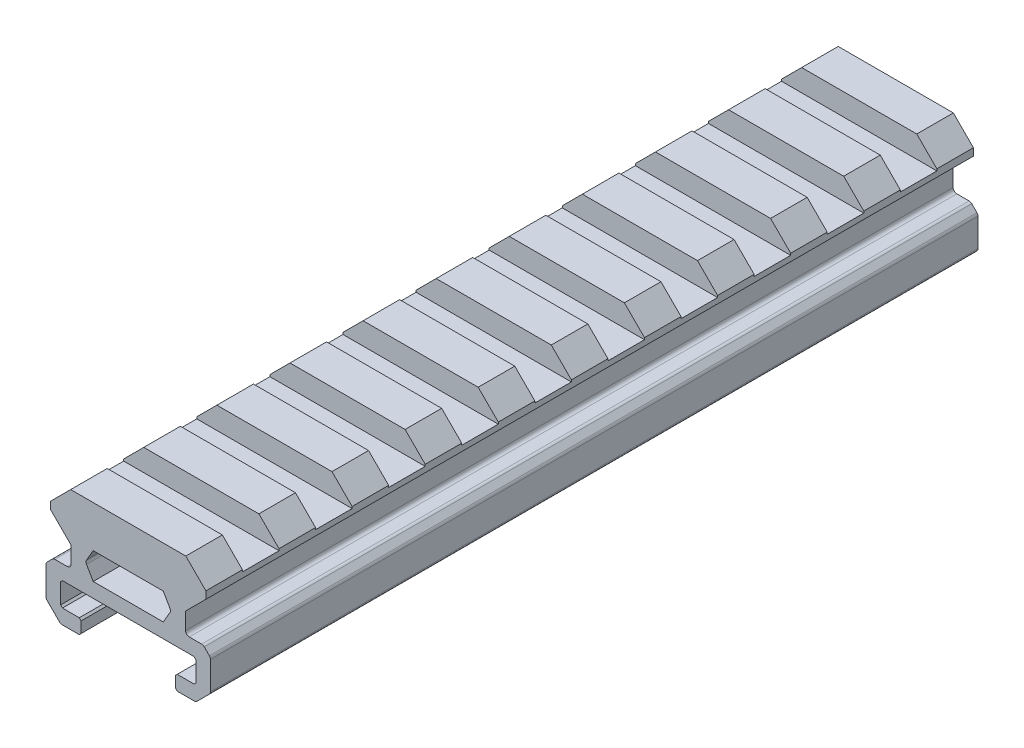
SolidWorks part; units mm, degrees
ref_plane "Front Plane" through (0, 0, 0) normal (0, 0, 1) x (1, 0, 0)
ref_plane "Bottom Plane" through (0, 0, 0) normal (0, 1, 0) x (1, 0, 0)
ref_plane "Right Plane" through (0, 0, 0) normal (1, 0, 0) x (0, 0, -1)
sketch "Sketch1" plane through (0, 0, 0) normal (0, 0, 1) x (1, 0, 0)
  line L0 (7.875, 11.35) -> (10.625, 8.6)
  line L1 (10.625, 7.6) -> (10.625, 8.6)
  line L2 (10.625, 7.6) -> (7.875, 4.85)
  line L3 (7.875, 4.85) -> (7.85, 4.85)
  line L4 (7.85, 4.85) -> (7.85, 2)
  line L5 (7.85, 2) -> (10.25, 2)
  line L6 (11.25, 1) -> (10.25, 2)
  line L7 (11.25, -3.25) -> (11.25, 1)
  line L8 (11.25, -3.25) -> (9.25, -5.25)
  line L9 (9.25, -5.25) -> (6.45, -5.25)
  line L10 (6.45, -5.25) -> (6.45, -3.25)
  line L11 (9.25, -3.25) -> (6.45, -3.25)
  line L14 (9.25, -3.25) -> (9.25, 0)
  line L18 (9.25, 0) -> (-9.25, 0)
  line L19 (-9.25, -3.25) -> (-9.25, 0)
  line L20 (-9.25, -3.25) -> (-6.45, -3.25)
  line L21 (-6.45, -5.25) -> (-6.45, -3.25)
  line L22 (-9.25, -5.25) -> (-6.45, -5.25)
  line L23 (-11.25, -3.25) -> (-9.25, -5.25)
  line L24 (-11.25, -3.25) -> (-11.25, 1)
  line L25 (-11.25, 1) -> (-10.25, 2)
  line L26 (-7.85, 2) -> (-10.25, 2)
  line L27 (-7.85, 4.85) -> (-7.85, 2)
  line L28 (-7.875, 4.85) -> (-7.85, 4.85)
  line L32 (-7.875, 11.35) -> (7.875, 11.35)
  line L33 (-10.625, 7.6) -> (-7.875, 4.85)
  line L34 (-10.625, 7.6) -> (-10.625, 8.6)
  line L35 (-7.875, 11.35) -> (-10.625, 8.6)
  line L36 (0, -1000) -> (0, 49000) construction
  point P0 (-9.25, -1.625)
  point P22 (0, 11.35)
  point P35 (0, 0)
  dimension "D2" = 3.25
  dimension "D3" = 9.35
  dimension "D4" = 15.75
  dimension "D5" = 21.25
  dimension "D6" = 7.85
  dimension "D7" = 9.25
  dimension "D8" = 2
  dimension "D9" = 6.45
  dimension "D10" = 45
  dimension "D11" = 45
  dimension "D12" = 45
  dimension "D13" = 45
  dimension "D14" = 1
  dimension "D15" = 2
  dimension "D16" = 2
  dimension "D17" = 1
  dimension "D18" = 2
  dimension "D19" = 18.5
  dimension "D20" = 2.8
  dimension "D21" = 12.9
extrude "Boss-Extrude1" add sketch "Sketch1" along normal blind 105
sketch "Sketch2" plane through (0, 0, 0) normal (1, 0, 0) x (0, 0, -1)
  line L0 (-995.4377, 11.35) -> (49004.5623, 11.35) construction
  line L16 (5, 11.35) -> (0, 11.35)
  line L17 (5, 11.35) -> (5, 8.35)
  line L18 (5, 8.35) -> (0, 8.35)
  line L23 (0, 11.35) -> (0, 8.35)
  line L81 (-105, 11.35) -> (0, 11.35) construction
  line L92 (-5, 11.35) -> (-10, 11.35)
  line L97 (-5, 11.35) -> (-5, 8.35)
  line L98 (-5, 8.35) -> (-10, 8.35)
  line L99 (-10, 11.35) -> (-10, 8.35)
  line L100 (-15, 11.35) -> (-20, 11.35)
  line L101 (-15, 11.35) -> (-15, 8.35)
  line L102 (-15, 8.35) -> (-20, 8.35)
  line L103 (-20, 11.35) -> (-20, 8.35)
  line L104 (-25, 11.35) -> (-30, 11.35)
  line L105 (-25, 11.35) -> (-25, 8.35)
  line L106 (-25, 8.35) -> (-30, 8.35)
  line L107 (-30, 11.35) -> (-30, 8.35)
  line L108 (-35, 11.35) -> (-40, 11.35)
  line L109 (-35, 11.35) -> (-35, 8.35)
  line L110 (-35, 8.35) -> (-40, 8.35)
  line L111 (-40, 11.35) -> (-40, 8.35)
  line L112 (-45, 11.35) -> (-50, 11.35)
  line L113 (-45, 11.35) -> (-45, 8.35)
  line L114 (-45, 8.35) -> (-50, 8.35)
  line L115 (-50, 11.35) -> (-50, 8.35)
  line L116 (-55, 11.35) -> (-60, 11.35)
  line L117 (-55, 11.35) -> (-55, 8.35)
  line L118 (-55, 8.35) -> (-60, 8.35)
  line L119 (-60, 11.35) -> (-60, 8.35)
  line L120 (-65, 11.35) -> (-70, 11.35)
  line L121 (-65, 11.35) -> (-65, 8.35)
  line L122 (-65, 8.35) -> (-70, 8.35)
  line L123 (-70, 11.35) -> (-70, 8.35)
  line L124 (-75, 11.35) -> (-80, 11.35)
  line L125 (-75, 11.35) -> (-75, 8.35)
  line L126 (-75, 8.35) -> (-80, 8.35)
  line L127 (-80, 11.35) -> (-80, 8.35)
  line L128 (-85, 11.35) -> (-90, 11.35)
  line L129 (-85, 11.35) -> (-85, 8.35)
  line L130 (-85, 8.35) -> (-90, 8.35)
  line L131 (-90, 11.35) -> (-90, 8.35)
  line L132 (-95, 11.35) -> (-100, 11.35)
  line L133 (-95, 11.35) -> (-95, 8.35)
  line L134 (-95, 8.35) -> (-100, 8.35)
  line L135 (-100, 11.35) -> (-100, 8.35)
  line L136 (5, 11.35) -> (-5, 11.35) construction
  dimension "D1" = 5
  dimension "D2" = 3
  dimension "D3" = 10
extrude "Cut-Extrude1" cut sketch "Sketch2" against normal through all both and the other way through all contours L23 | L99 | L103 | L107 | L111 | L115 | L119 | L123 | L127 | L131 | L16 L23 L18 L17 | L92 L99 L98 L97 | L100 L103 L102 L101 | L104 L107 L106 L105 | L108 L111 L110 L109 | L112 L115 L114 L113 | L116 L119 L118 L117 | L120 L123 L122 L121 | L124 L127 L126 L125 | L128 L131 L130 L129 | L132 L135 L134 L133 region at (0, 9.85, -2.5) region at (0, 9.85, 7.5) region at (0, 9.85, 17.5) region at (0, 9.85, 27.5) region at (0, 9.85, 37.5) region at (0, 9.85, 47.5) region at (0, 9.85, 57.5) region at (0, 9.85, 67.5) region at (0, 9.85, 77.5) region at (0, 9.85, 87.5) region at (0, 9.85, 97.5)
sketch "Sketch3" plane through (0, 0, 0) normal (0, 0, 1) x (1, 0, 0)
  line L0 (-7.85, 4.85) -> (-7.85, 2) construction
  line L1 (-10.625, 7.6) -> (-7.875, 4.85) construction
  line L2 (-2.1587, 4.7401) -> (-2.686, 5.6534) construction
  line L3 (-5.85, 3.8267) -> (-4.7953, 2)
  line L4 (-4.7953, 2) -> (-2.686, 2)
  line L5 (-2.686, 2) -> (-2.1587, 2.9134) construction
  line L6 (-1.6314, 3.8267) -> (-2.1587, 4.7401) construction
  line L7 (-2.686, 5.6534) -> (-4.7953, 5.6534)
  line L8 (-4.7953, 5.6534) -> (-5.85, 3.8267)
  line L9 (7.85, 2) -> (7.85, 4.85) construction
  line L10 (7.875, 4.85) -> (10.625, 7.6) construction
  line L11 (7.85, 2) -> (7.85, 4.85) construction
  line L12 (7.875, 4.85) -> (10.625, 7.6) construction
  line L13 (-7.85, 4.85) -> (-7.85, 2) construction
  line L14 (-10.625, 7.6) -> (-7.875, 4.85) construction
  line L15 (5.85, 2) -> (5.85, 5.6534) construction
  line L16 (5.85, 5.6534) -> (6.7966, 6.6) construction
  line L17 (-5.85, 5.6534) -> (-5.85, 2) construction
  line L18 (-6.7966, 6.6) -> (-5.85, 5.6534) construction
  line L19 (-5.85, 2) -> (5.85, 2) construction
  line L20 (5.85, 2) -> (5.85, 4.85) construction
  line L21 (-5.85, 4.85) -> (-5.85, 2) construction
  line L22 (-9.2108, 9.0142) -> (-6.4608, 6.2642) construction
  line L23 (6.4608, 6.2642) -> (9.2108, 9.0142) construction
  line L24 (6.7966, 6.6) -> (-6.7966, 6.6) construction
  line L25 (10.625, 7.6) -> (10.625, 8.6) construction
  line L26 (10.625, 8.6) -> (7.875, 11.35) construction
  line L27 (7.875, 11.35) -> (-7.875, 11.35) construction
  line L28 (-7.875, 11.35) -> (-10.625, 8.6) construction
  line L29 (-10.625, 8.6) -> (-10.625, 7.6) construction
  line L30 (10.625, 7.6) -> (10.625, 8.6) construction
  line L31 (10.625, 8.6) -> (7.875, 11.35) construction
  line L32 (7.875, 11.35) -> (-7.875, 11.35) construction
  line L33 (-7.875, 11.35) -> (-10.625, 8.6) construction
  line L34 (-10.625, 8.6) -> (-10.625, 7.6) construction
  line L35 (-5.85, 5.6534) -> (5.85, 5.6534) construction
  line L36 (-2.1587, 2.9134) -> (-1.6314, 3.8267) construction
  line L37 (0, -1000) -> (0, 49000) construction
  line L38 (4.7953, 5.6534) -> (5.85, 3.8267)
  line L39 (5.85, 3.8267) -> (4.7953, 2)
  line L40 (2.1587, 2.9134) -> (1.6314, 3.8267) construction
  line L41 (1.6314, 3.8267) -> (2.1587, 4.7401) construction
  line L42 (2.686, 2) -> (2.1587, 2.9134) construction
  line L43 (2.1587, 4.7401) -> (2.686, 5.6534) construction
  line L44 (2.686, 5.6534) -> (4.7953, 5.6534)
  line L45 (4.7953, 2) -> (2.686, 2)
  line L46 (-2.686, 5.6534) -> (2.686, 5.6534)
  line L47 (-2.686, 2) -> (2.686, 2)
  circle A0 centre (-3.7407, 3.8267) radius 1.8267 construction
  circle A1 centre (3.7407, 3.8267) radius 1.8267 construction
  dimension "D2" = 1
  dimension "D1" = 2
extrude "Cut-Extrude2" cut sketch "Sketch3" along normal up to next
chamfer "Chamfer1" distance 0.25 angle 45 8 edges at (9.25, 0, 52.5) (9.25, -3.25, 52.5) (6.45, -3.25, 52.5) (6.45, -5.25, 52.5) (-9.25, 0, 52.5) (-9.25, -3.25, 52.5) (-6.45, -3.25, 52.5) (-6.45, -5.25, 52.5)
fillet "Fillet1" radius 0.5 12 edges at (-9.25, -5.25, 52.5) (-11.25, -3.25, 52.5) (9.25, -5.25, 52.5) (11.25, -3.25, 52.5) (11.25, 1, 52.5) (10.25, 2, 52.5) (-11.25, 1, 52.5) (-10.25, 2, 52.5) (-7.85, 2, 52.5) (7.85, 2, 52.5) (5.85, 3.8267, 52.5) (-5.85, 3.8267, 52.5)
